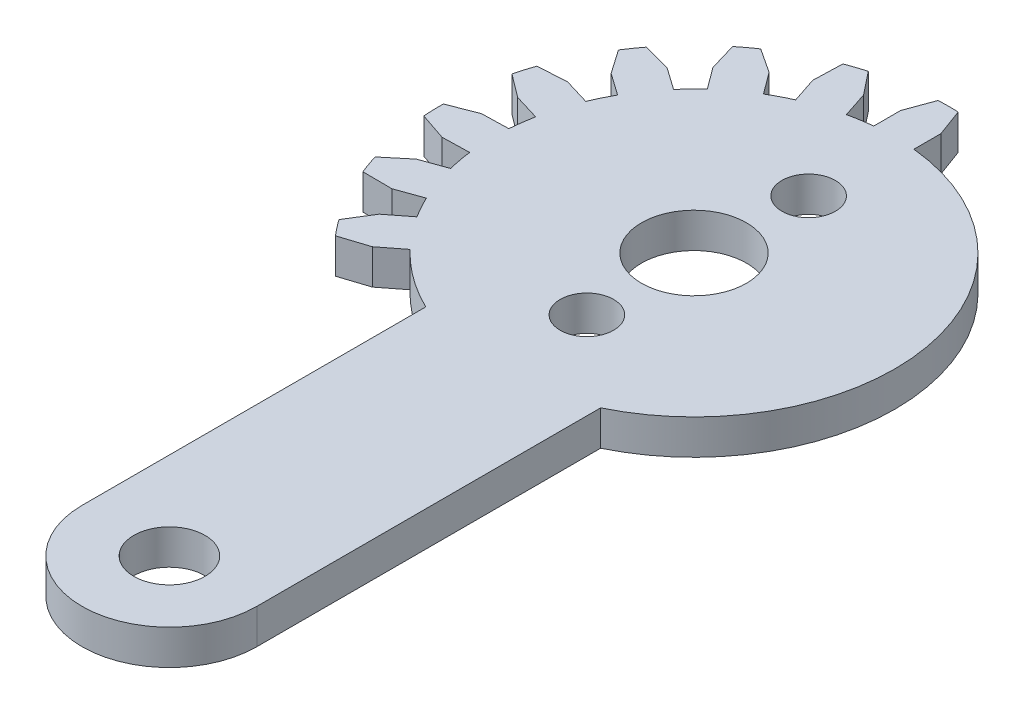
SolidWorks part; units mm, degrees
ref_plane "Alzado" through (0, 0, 0) normal (0, 0, 1) x (1, 0, 0)
ref_plane "Planta" through (0, 0, 0) normal (0, 1, 0) x (1, 0, 0)
ref_plane "Vista lateral" through (0, 0, 0) normal (1, 0, 0) x (0, 0, -1)
sketch "Croquis1" plane through (0, 0, 0) normal (0, 1, 0) x (1, 0, 0)
  line L0 (0, 0) -> (0, -30) construction
  line L1 (-5, -10.3395) -> (-5, -30)
  line L2 (5, -10.3395) -> (5, -30)
  line L5 (0, 0) -> (12.7, 0) construction
  arc A0 (5, -10.3395) -> (-5, -10.3395) centre (0, 0) ccw
  arc A1 (-5, -30) -> (5, -30) centre (0, -30) ccw
  circle A2 centre (0, -30) radius 2.0343
  circle A3 centre (0, 0) radius 3
  circle A4 centre (0, 0) radius 11.485 construction
  point P9 (0, 11.485)
  point P10 (0, -35)
  dimension "D1" = 22.97
  dimension "D3" = 30
  dimension "D2" = 10
  dimension "D4" = 6
extrude "Saliente-Extruir1" add sketch "Croquis1" along normal blind 2
sketch "Croquis3" plane through (0, 0, 0) normal (0, 1, 0) x (1, 0, 0)
  line L0 (0, 11.485) -> (0, 0) construction
  line L1 (0, 11.485) -> (0, 14.5475) construction
  line L2 (-1.1484, 12.9655) -> (-1.1484, 11.4274)
  line L3 (0.5742, 14.5362) -> (1.1484, 12.9655)
  line L4 (-0.5742, 14.5362) -> (-1.1484, 12.9655)
  line L5 (1.1484, 12.9655) -> (1.1484, 11.4274)
  line L6 (0, 0) -> (11.485, 0) construction
  circle A0 centre (0, 0) radius 14.5475 construction
  circle A1 centre (0, 0) radius 11.485 construction
  circle A2 centre (0, 0) radius 13.0162 construction
  arc A3 (5, -10.3395) -> (-5, -10.3395) centre (0, 0) ccw construction
  arc A4 (0.5742, 14.5362) -> (-0.5742, 14.5362) centre (0, 0) ccw
  arc A5 (1.1484, 11.4274) -> (-1.1484, 11.4274) centre (0, 0) ccw
  point P16 (0, 13.0162)
  dimension "D1" = 3.0625
  dimension "D2" = 1.1484
  dimension "D3" = 2.2969
extrude "Saliente-Extruir2" add sketch "Croquis3" along normal up to surface (2 mm away) up to face at (0, 2, 32.0343)
pattern_circular "MatrizC1" count 8 over 128 about axis through (0, 2, 0) along (0, 1, 0) of "Saliente-Extruir2"
sketch "Croquis4" plane through (0, 0, 0) normal (0, -1, 0) x (1, 0, 0)
  line L0 (0, 0) -> (0.6418, -8.7504) construction
  circle A0 centre (0.4481, -6.1086) radius 1.53
  circle A1 centre (0, 0) radius 6.125 construction
  circle A2 centre (0, 6.125) radius 1.53
  dimension "D1" = 3.06
  dimension "D2" = 12.25
extrude "Cortar-Extruir1" cut sketch "Croquis4" against normal blind 10
